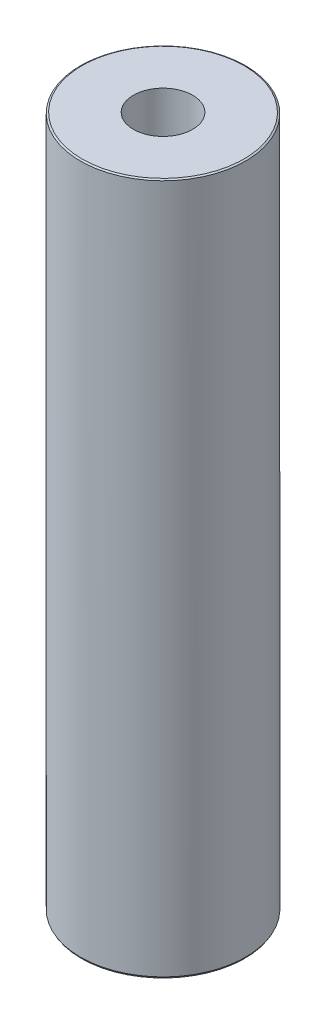
SolidWorks part; units mm, degrees
ref_plane "Front Plane" through (0, 0, 0) normal (0, 0, 1) x (1, 0, 0)
ref_plane "Top Plane" through (0, 0, 0) normal (0, 1, 0) x (1, 0, 0)
ref_plane "Right Plane" through (0, 0, 0) normal (1, 0, 0) x (0, 0, -1)
sketch "Sketch1" plane through (0, 0, 0) normal (0, 1, 0) x (1, 0, 0)
  circle A0 centre (0, 0) radius 25
  dimension "SHAFT_OD" = 50
extrude "Boss-Extrude1" add sketch "Sketch1" along normal blind 209.4548
sketch "Sketch2" plane through (0, 0, 0) normal (0, 1, 0) x (1, 0, 0)
  circle A0 centre (0, 0) radius 8.9606
  dimension "BORE_D" = 17.9213
extrude "Cut-Extrude1" cut sketch "Sketch2" along normal through all
chamfer "Chamfer1" distance 0.2885 angle 60 2 edges at (0, 209.4548, 25) (0, 0, 25) first distance on face at (0, 209.4548, 25) first distance on face at (0, 0, 8.9606)
